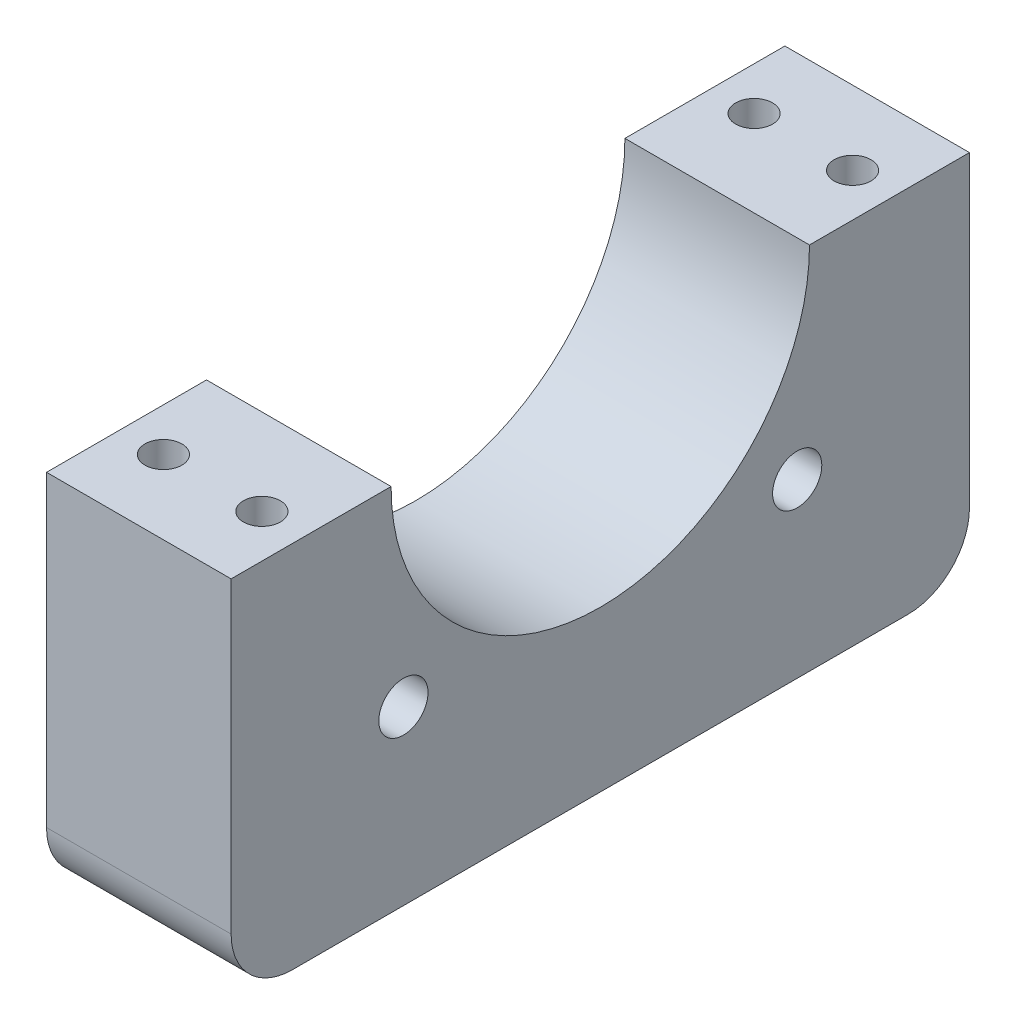
SolidWorks part; units mm, degrees
material "ABS"
ref_plane "Front Plane" through (0, 0, 0) normal (0, 0, 1) x (1, 0, 0)
ref_plane "Top Plane" through (0, 0, 0) normal (0, 1, 0) x (1, 0, 0)
ref_plane "Right Plane" through (0, 0, 0) normal (1, 0, 0) x (0, 0, -1)
other "Configuration Table"
sketch "Sketch1" plane through (0, 0, 0) normal (0, 1, 0) x (1, 0, 0)
  line L1 (7.5, -30) -> (-7.5, -30)
  line L2 (7.5, -30) -> (7.5, 30)
  line L3 (7.5, 30) -> (-7.5, 30)
  line L4 (-7.5, -30) -> (-7.5, 30)
  line L5 (7.5, -30) -> (-7.5, 30) construction
  line L6 (7.5, 30) -> (-7.5, -30) construction
  point P0 (0, 0)
  dimension "D1" = 60
  dimension "D2" = 15
extrude "Boss-Extrude1" add sketch "Sketch1" along normal blind 70
sketch "Sketch2" plane through (7.5, 0, 0) normal (1, 0, 0) x (0, 0, -1)
  line L0 (-30, 0) -> (30, 0) construction
  circle A0 centre (0, 30) radius 17
  point P9 (0, 30)
  dimension "D1" = 34
  dimension "D2" = 30
extrude "Cut-Extrude1" cut sketch "Sketch2" against normal blind 70
sketch "Sketch3" plane through (7.5, 0, 0) normal (1, 0, 0) x (0, 0, -1)
  line L0 (-30, 30) -> (30, 30)
  line L1 (30, 70) -> (30, 0) construction
  line L2 (-30, 30) -> (-30, 70)
  line L3 (-30, 70) -> (30, 70)
  line L4 (30, 70) -> (30, 30)
  point P6 (0, 30)
extrude "Cut-Extrude2" cut sketch "Sketch3" against normal blind 29
sketch "Sketch4" plane through (0, 30, 0) normal (0, 1, 0) x (1, 0, 0)
  line L0 (-7.5, 17) -> (-7.5, 30) construction
  line L1 (7.5, 17) -> (7.5, 30) construction
  line L2 (-7.5, 30) -> (7.5, 30) construction
  line L3 (-7.5, -30) -> (-7.5, -17) construction
  line L4 (7.5, -30) -> (7.5, -17) construction
  line L5 (-7.5, -30) -> (7.5, -30) construction
  circle A0 centre (-4, 24) radius 1.5
  circle A1 centre (4, 24) radius 1.5
  circle A2 centre (-4, -24) radius 1.5
  circle A3 centre (4, -24) radius 1.5
  dimension "D1" = 3
  dimension "D2" = 3
  dimension "D7" = 3
  dimension "D8" = 3
  dimension "D3" = 3.5
  dimension "D4" = 3.5
  dimension "D5" = 6
  dimension "D6" = 6
  dimension "D9" = 3.5
  dimension "D10" = 3.5
  dimension "D11" = 6
  dimension "D12" = 6
extrude "Cut-Extrude3" cut sketch "Sketch4" against normal blind 43
sketch "Sketch5" plane through (7.5, 0, 0) normal (1, 0, 0) x (0, 0, -1)
  line L1 (16, 14) -> (-16, 14) construction
  line L2 (16, 14) -> (16, 46) construction
  line L3 (16, 46) -> (-16, 46) construction
  line L4 (-16, 14) -> (-16, 46) construction
  line L5 (16, 14) -> (-16, 46) construction
  line L6 (16, 46) -> (-16, 14) construction
  circle A0 centre (-16, 14) radius 2
  circle A1 centre (16, 14) radius 2
  point P0 (0, 30)
  dimension "D2" = 4
  dimension "D3" = 4
  dimension "D1" = 32
extrude "Cut-Extrude4" cut sketch "Sketch5" against normal blind 10
sketch "Sketch7" plane through (0, 0, 0) normal (0, -1, 0) x (1, 0, 0)
  circle A0 centre (-4, 24) radius 3
  circle A1 centre (4, 24) radius 3
  circle A2 centre (-4, -24) radius 3
  circle A3 centre (4, -24) radius 3
  dimension "D1" = 6
  dimension "D2" = 6
  dimension "D3" = 6
  dimension "D4" = 6
extrude "Cut-Extrude5" cut sketch "Sketch7" against normal blind 10
fillet "Fillet1" radius 5 2 edges at (0, 0, 30) (0, 0, -30)
